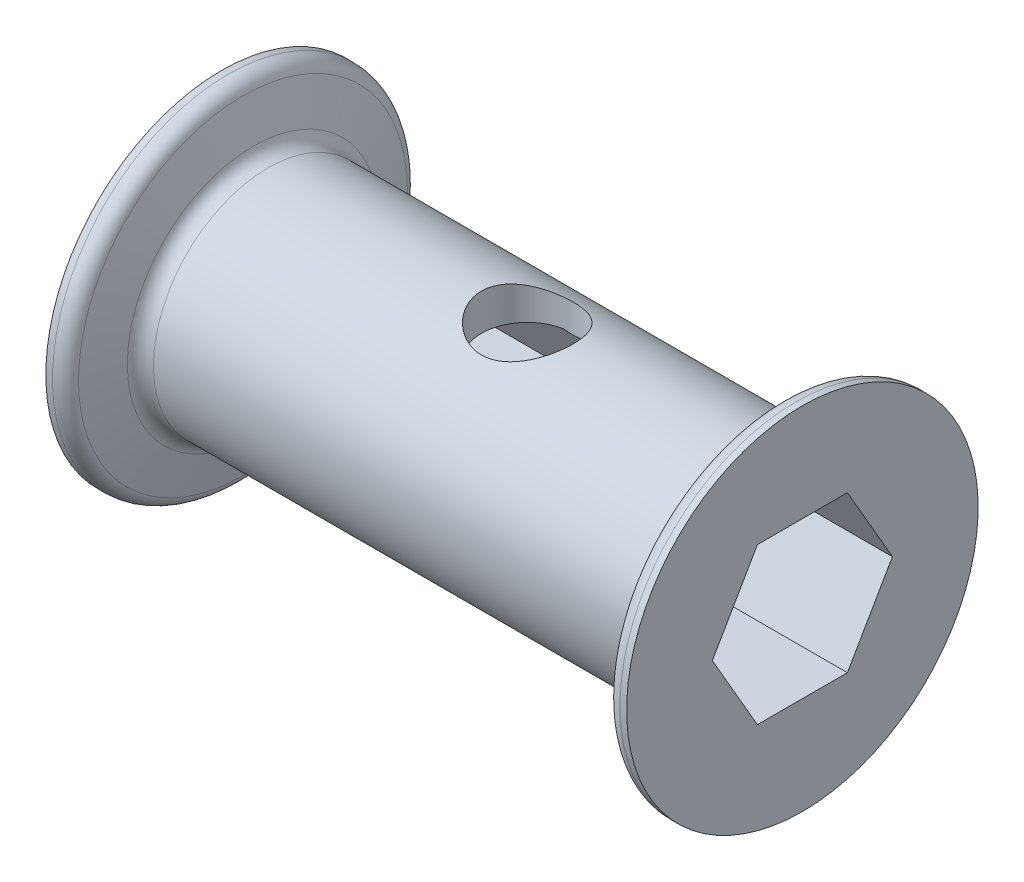
SolidWorks part; units mm, degrees
ref_plane "Front Plane" through (0, 0, 0) normal (0, 0, 1) x (1, 0, 0)
ref_plane "Top Plane" through (0, 0, 0) normal (0, 1, 0) x (1, 0, 0)
ref_plane "Right Plane" through (0, 0, 0) normal (1, 0, 0) x (0, 0, -1)
sketch "Sketch1" plane through (0, 0, 0) normal (0, 0, 1) x (1, 0, 0)
  line L0 (0, 0) -> (48.26, 0)
  line L1 (48.26, 0) -> (48.26, 14.605)
  line L2 (48.26, 14.605) -> (46.736, 14.605)
  line L3 (46.736, 14.605) -> (45.3748, 9.525)
  line L4 (45.3748, 9.525) -> (2.8852, 9.525)
  line L5 (2.8852, 9.525) -> (1.524, 14.605)
  line L6 (1.524, 14.605) -> (0, 14.605)
  line L7 (0, 14.605) -> (0, 0)
  line L8 (48.26, 0) -> (36.7691, 0) construction
  dimension "D1" = 48.26
  dimension "D2" = 5.08
  dimension "D3" = 5.08
  dimension "D4" = 19.05
  dimension "D5" = 15
  dimension "D6" = 1.524
revolve "Revolve1" add sketch "Sketch1" angle 360 about L8
sketch "Sketch2" plane through (0, 0, 0) normal (-1, 0, 0) x (0, 0, 1)
  line L0 (-14.605, 0) -> (14.605, 0) construction
  line L1 (7.479, 0) -> (3.7395, 6.477)
  line L2 (3.7395, 6.477) -> (-3.7395, 6.477)
  line L3 (-3.7395, 6.477) -> (-7.479, 0)
  line L4 (-7.479, 0) -> (-3.7395, -6.477)
  line L5 (-3.7395, -6.477) -> (3.7395, -6.477)
  line L6 (3.7395, -6.477) -> (7.479, 0)
  circle A0 centre (0, 0) radius 6.477 construction
  circle A2 centre (0, 0) radius 14.605 construction
  dimension "D1" = 12.954
  dimension "D2" = 7.126
extrude "Cut-Extrude1" cut sketch "Sketch2" against normal through all
fillet "Fillet1" radius 1.27 4 edges at (2.8852, 9.525, 0) (1.524, 14.605, 0) (46.736, 14.605, 0) (45.3748, 9.525, 0)
sketch "Sketch3" plane through (0, 0, 0) normal (0, 0, 1) x (1, 0, 0)
  line L6 (48.26, -14.605) -> (48.26, 14.605) construction
  line L12 (0, 0) -> (31.817, 0) construction
  line L13 (48.26, 14.605) -> (47.7105, 14.605) construction
  line L14 (47.7105, -14.605) -> (48.26, -14.605) construction
  line L15 (27.305, -14.605) -> (25.4, -14.605)
  line L16 (27.305, -14.605) -> (27.305, -0.0253)
  line L17 (25.4, -14.605) -> (25.4, 14.605)
  line L18 (29.21, -0.0253) -> (27.305, -0.0253)
  line L19 (25.4, 14.605) -> (25.4, 15.4744) construction
  line L20 (25.4, 14.605) -> (29.21, 14.605)
  line L21 (29.21, 14.605) -> (29.21, -0.0253)
  dimension "D1" = 7.62
  dimension "D2" = 3.81
  dimension "D3" = 22.86
  dimension "D4" = 0.0506
revolve "Cut-Revolve1" cut sketch "Sketch3" angle 360 about L19
